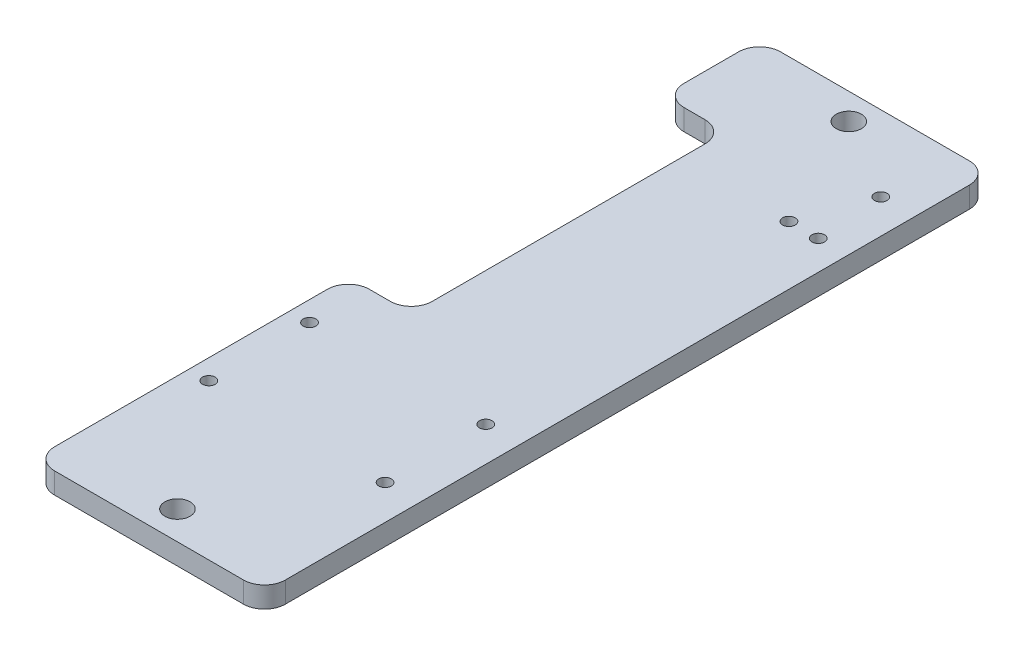
SolidWorks part; units mm, degrees
ref_plane "Front Plane" through (0, 0, 0) normal (0, 0, 1) x (1, 0, 0)
ref_plane "Top Plane" through (0, 0, 0) normal (0, 1, 0) x (1, 0, 0)
ref_plane "Right Plane" through (0, 0, 0) normal (1, 0, 0) x (0, 0, -1)
sketch "Sketch1" plane through (0, 0, 0) normal (0, 1, 0) x (1, 0, 0)
  line L1 (0, 0) -> (200, 0)
  line L2 (0, 0) -> (0, 200)
  line L3 (0, 200) -> (200, 200)
  line L4 (200, 0) -> (200, 200)
  dimension "D1" = 200
  dimension "D2" = 200
extrude "Boss-Extrude1" add sketch "Sketch1" along normal blind 5
sketch "Sketch2" plane through (0, 5, 0) normal (0, 1, 0) x (1, 0, 0)
  line L0 (0, 100) -> (200, 100) construction
  line L1 (0, 200) -> (0, 0) construction
  line L2 (200, 0) -> (200, 200) construction
  line L4 (50, 50) -> (150, 50)
  line L5 (50, 50) -> (50, 150)
  line L6 (50, 150) -> (150, 150)
  line L7 (150, 50) -> (150, 150)
  line L8 (50, 50) -> (150, 150) construction
  line L9 (50, 150) -> (150, 50) construction
  point P6 (100, 100)
  dimension "D1" = 100
  dimension "D2" = 100
extrude "Cut-Extrude1" cut sketch "Sketch2" against normal blind 10
fillet "Fillet1" radius 10 4 edges at (50, 2.5, -50) (150, 2.5, -50) (150, 2.5, -150) (50, 2.5, -150)
fillet "Fillet2" radius 10 4 edges at (200, 2.5, 0) (0, 2.5, 0) (0, 2.5, -200) (200, 2.5, -200)
sketch "Sketch3" plane through (0, 5, 0) normal (0, 1, 0) x (1, 0, 0)
  circle A0 centre (10, 190) radius 3
  circle A1 centre (190, 190) radius 3
  circle A2 centre (190, 10) radius 3
  circle A3 centre (10, 10) radius 3
  arc A4 (10, 200) -> (0, 190) centre (10, 190) ccw construction
  arc A5 (200, 190) -> (190, 200) centre (190, 190) ccw construction
  arc A6 (190, 0) -> (200, 10) centre (190, 10) ccw construction
  arc A7 (0, 10) -> (10, 0) centre (10, 10) ccw construction
  dimension "D1" = 6
  dimension "D2" = 6
  dimension "D3" = 6
  dimension "D4" = 6
extrude "Cut-Extrude2" cut sketch "Sketch3" against normal blind 10
sketch "Sketch4" plane through (0, 5, 0) normal (0, 1, 0) x (1, 0, 0)
  line L0 (0, 100) -> (200, 100) construction
  line L1 (0, 190) -> (0, 10) construction
  line L2 (200, 10) -> (200, 190) construction
  line L4 (154.75, 48) -> (196.75, 48) construction
  line L5 (154.75, 48) -> (154.75, 24) construction
  line L6 (154.75, 24) -> (196.75, 24) construction
  line L7 (196.75, 48) -> (196.75, 24) construction
  line L8 (191, 126) -> (198, 126) construction
  line L9 (87.4, -90.3308) -> (287.4, -90.3308) construction
  line L10 (242.15, -142.3308) -> (284.15, -142.3308) construction
  line L11 (284.15, -142.3308) -> (284.15, -166.3308) construction
  line L12 (278.4, -64.3308) -> (285.4, -64.3308) construction
  line L13 (242.15, -166.3308) -> (284.15, -166.3308) construction
  line L14 (242.15, -142.3308) -> (242.15, -166.3308) construction
  circle A0 centre (198, 126) radius 1.5
  circle A1 centre (191, 126) radius 1.5
  circle A2 centre (196.89, 142) radius 1.5
  circle A3 centre (154.75, 48) radius 1.5
  circle A4 centre (196.75, 48) radius 1.5
  circle A5 centre (196.75, 24) radius 1.5
  circle A6 centre (154.75, 24) radius 1.5
  circle A7 centre (242.15, -166.3308) radius 1.5
  circle A8 centre (285.4, -64.3308) radius 1.5
  circle A9 centre (242.15, -142.3308) radius 1.5
  circle A10 centre (284.29, -48.3308) radius 1.5
  circle A11 centre (284.15, -142.3308) radius 1.5
  circle A12 centre (284.15, -166.3308) radius 1.5
  circle A13 centre (278.4, -64.3308) radius 1.5
  dimension "D1" = 3
  dimension "D2" = 3
  dimension "D3" = 7
  dimension "D4" = 26
  dimension "D5" = 16
  dimension "D6" = 3
  dimension "D7" = 1.11
  dimension "D8" = 3
  dimension "D9" = 3
  dimension "D10" = 3
  dimension "D11" = 3
  dimension "D15" = 2
  dimension "D17" = 3
  dimension "D18" = 3
  dimension "D22" = 3
  dimension "D24" = 3
  dimension "D25" = 3
  dimension "D26" = 3
  dimension "D27" = 3
  dimension "D12" = 42
  dimension "D13" = 24
  dimension "D14" = 78
  dimension "D16" = 3.25
  dimension "D19" = 7
  dimension "D20" = 26
  dimension "D21" = 16
  dimension "D23" = 1.11
  dimension "D28" = 42
  dimension "D29" = 24
  dimension "D30" = 78
extrude "Cut-Extrude3" cut sketch "Sketch4" against normal blind 10
sketch "Sketch5" plane through (0, 5, 0) normal (0, 1, 0) x (1, 0, 0)
  line L0 (0, 190) -> (0, 10)
  line L1 (10, 200) -> (190, 200)
  line L2 (200, 190) -> (200, 10)
  line L3 (10, 0) -> (190, 0)
  line L4 (0, 100) -> (200, 100) construction
  line L6 (-5, -5) -> (205, -5)
  line L7 (-5, -5) -> (-5, 205)
  line L8 (-5, 205) -> (205, 205)
  line L9 (205, -5) -> (205, 205)
  line L10 (-5, -5) -> (205, 205) construction
  line L11 (-5, 205) -> (205, -5) construction
  arc A0 (0, 190) -> (10, 200) centre (10, 190) cw
  arc A1 (190, 200) -> (200, 190) centre (190, 190) cw
  arc A2 (200, 10) -> (190, 0) centre (190, 10) cw
  arc A3 (190, 0) -> (200, 10) centre (190, 10) ccw construction
  arc A4 (0, 10) -> (10, 0) centre (10, 10) ccw
  point P24 (100, 100)
  dimension "D1" = 5
  dimension "D2" = 5
extrude "Boss-Extrude2" add sketch "Sketch5" against normal blind 5
fillet "Fillet3" radius 10 4 edges at (205, 2.5, -205) (-5, 2.5, -205) (-5, 2.5, 5) (205, 2.5, 5)
ref_plane "Plane1" through (100, 0, 0) normal (-1, 0, 0) x (0, 0, 1)
ref_plane "Plane2" through (0, 0, -100) normal (0, 0, 1) x (1, 0, 0)
ref_axis "Axis1" through (100, 5.25, -100) along (0, -1, 0)
pattern_circular "CirPattern1" count 4 over 360 about axis through (100, 5.25, -100) along (0, -1, 0) of "Cut-Extrude3"
sketch "Sketch6" plane through (0, 5, 0) normal (0, 1, 0) x (1, 0, 0)
  line L0 (205, 5) -> (205, 195) construction
  line L1 (205, 149) -> (150, 149)
  line L2 (205, 149) -> (205, 17)
  line L3 (205, 17) -> (150, 17)
  line L4 (150, 149) -> (150, 17)
  line L5 (150, 60) -> (150, 140) construction
  circle A0 centre (196.89, 142) radius 1.5 construction
  circle A1 centre (196.75, 24) radius 1.5 construction
  dimension "D1" = 7
  dimension "D2" = 7
extrude "Cut-Extrude4" cut sketch "Sketch6" against normal blind 10 flip side to cut
sketch "Sketch7" plane through (0, 5, 0) normal (0, 1, 0) x (1, 0, 0)
  line L0 (177.5, 17) -> (177.5, 149) construction
  line L1 (150, 17) -> (205, 17) construction
  line L2 (205, 149) -> (150, 149) construction
  line L3 (150, 83) -> (205, 83) construction
  line L4 (150, 17) -> (150, 149) construction
  line L5 (205, 17) -> (205, 149) construction
  circle A0 centre (177.5, 113) radius 2.5
  circle A1 centre (177.5, 53) radius 2.5
  dimension "D1" = 5
  dimension "D2" = 30
extrude "Cut-Extrude5" [suppressed] cut sketch "Sketch7" against normal blind 10
fillet "Fillet4" [suppressed] radius 5
sketch "Sketch8" plane through (0, 5, 0) normal (0, 1, 0) x (1, 0, 0)
  line L0 (150, 83) -> (205, 83) construction
  line L1 (150, 17) -> (150, 149) construction
  line L2 (205, 17) -> (205, 149) construction
  line L3 (205, 17) -> (205, -13)
  line L4 (150, 149) -> (205, 149)
  line L5 (150, 149) -> (150, 179)
  line L6 (150, 179) -> (205, 179)
  line L7 (205, 149) -> (205, 179)
  line L8 (150, -13) -> (205, -13)
  line L9 (150, 17) -> (150, -13)
  line L10 (150, 17) -> (205, 17)
  dimension "D1" = 30
extrude "Boss-Extrude3" add sketch "Sketch8" against normal blind 5
sketch "Sketch9" plane through (0, 5, 0) normal (0, 1, 0) x (1, 0, 0)
  line L0 (150, 83) -> (205, 83) construction
  line L1 (150, -13) -> (150, 179) construction
  line L2 (205, -13) -> (205, 179) construction
  line L3 (177.5, 83) -> (177.5, 153.77) construction
  line L4 (177.5, 83) -> (177.5, -6.23) construction
  circle A0 centre (177.5, 153.77) radius 3
  circle A1 centre (177.5, -6.23) radius 3
  dimension "D1" = 6
  dimension "D3" = 160
  dimension "D2" = 70.77
extrude "Cut-Extrude6" cut sketch "Sketch9" against normal blind 5
fillet "Fillet5" [suppressed] radius 5
sketch "Sketch11" plane through (0, 5, 0) normal (0, 1, 0) x (1, 0, 0)
  line L0 (205, -13) -> (205, 179) construction
  line L1 (150, 179) -> (205, 179)
  line L2 (150, 179) -> (150, 160)
  line L3 (150, 160) -> (205, 160)
  line L4 (205, 179) -> (205, 160)
  dimension "D1" = 19
extrude "Cut-Extrude7" cut sketch "Sketch11" against normal blind 39
fillet "Fillet6" radius 5 4 edges at (205, 2.5, 13) (150, 2.5, 13) (150, 2.5, -160) (205, 2.5, -160)
sketch "Sketch12" plane through (0, 5, 0) normal (0, 1, 0) x (1, 0, 0)
  line L0 (150, -8) -> (150, 155) construction
  line L1 (150, 137) -> (165, 137)
  line L2 (150, 137) -> (150, 62)
  line L3 (150, 62) -> (165, 62)
  line L4 (165, 137) -> (165, 62)
  line L5 (155, -13) -> (200, -13) construction
  dimension "D1" = 75
  dimension "D2" = 15
  dimension "D3" = 75
extrude "Cut-Extrude8" cut sketch "Sketch12" against normal blind 10 contours L4 L3 L2 L1
fillet "Fillet7" radius 5 4 edges at (165, 2.5, -137) (165, 2.5, -62) (150, 2.5, -62) (150, 2.5, -137)
